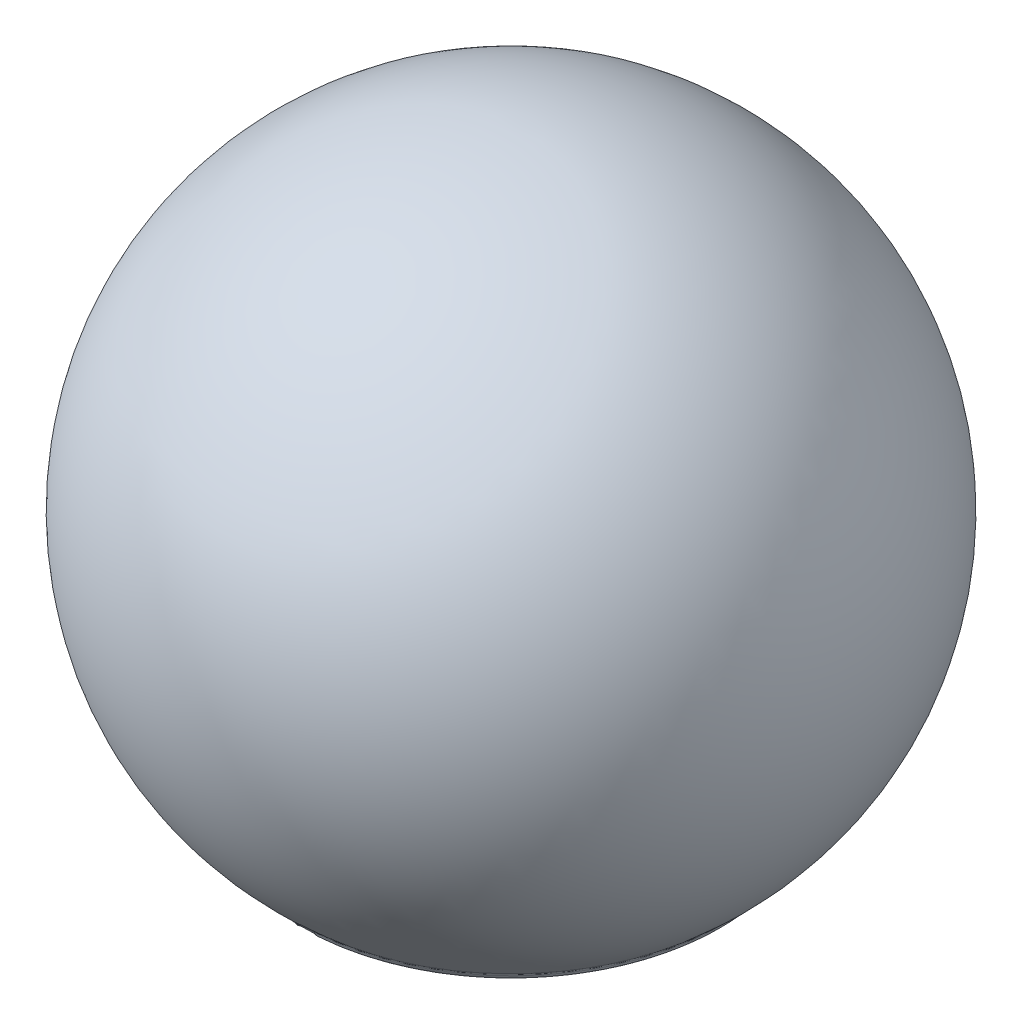
SolidWorks part; units mm, degrees
ref_plane "Front Plane" through (0, 0, 0) normal (0, 0, 1) x (1, 0, 0)
ref_plane "Top Plane" through (0, 0, 0) normal (0, 1, 0) x (1, 0, 0)
ref_plane "Right Plane" through (0, 0, 0) normal (1, 0, 0) x (0, 0, -1)
sketch "Sketch1" plane through (0, 0, 0) normal (0, 0, 1) x (1, 0, 0)
  line L0 (0, 74.75) -> (0, 73.175)
  line L1 (0, -73.175) -> (0, -74.75)
  arc A0 (0, -74.75) -> (0, 74.75) centre (0, 0) ccw
  arc A1 (0, -73.175) -> (0, 73.175) centre (0, 0) ccw
  dimension "D1" = 149.5
  dimension "D2" = 1.575
revolve "Revolve1" add sketch "Sketch1" angle 360 about L0
sketch "Sketch3" plane through (0, 0, 0) normal (0, 0, 1) x (1, 0, 0)
  line L0 (45.425, -57.3685) -> (-45.425, -57.3685)
  line L1 (0, -57.3685) -> (0, -74.75) construction
  line L5 (45.425, -57.3685) -> (47.9209, -57.3685)
  line L6 (47.9209, -57.3685) -> (47.9209, -74.75)
  line L8 (-47.9209, -74.75) -> (47.9209, -74.75)
  line L9 (-47.9209, -57.3685) -> (-47.9209, -74.75)
  line L10 (-45.425, -57.3685) -> (-47.9209, -57.3685)
  arc A1 (0, -73.175) -> (0, 73.175) centre (0, 0) ccw construction
  arc A2 (0, -74.75) -> (0, 74.75) centre (0, 0) ccw construction
  dimension "D1" = 45.425
extrude "Cut-Extrude1" cut sketch "Sketch3" against normal mid plane 130
sketch "Sketch4" plane through (0, 0, 0) normal (0, 0, 1) x (1, 0, 0)
  line L0 (47.9209, -57.3685) -> (47.9209, -58.8685)
  line L1 (47.9209, -58.8685) -> (45.425, -58.8685)
  line L2 (45.425, -58.8685) -> (45.425, -57.3685)
  line L3 (45.425, -57.3685) -> (47.9209, -57.3685)
  arc A0 (0, -74.75) -> (0, 74.75) centre (0, 0) ccw construction
  dimension "D1" = 1.5
revolve "Revolve2" add sketch "Sketch4" angle 360 about L1
fillet "Fillet1" radius 1.5 1 edges at (-47.9209, -58.8685, 0)
fillet "Fillet2" radius 1.5 1 edges at (-47.9209, -57.3685, 0)
fillet "Fillet3" radius 1.5 1 edges at (-45.425, -57.3685, 0)
